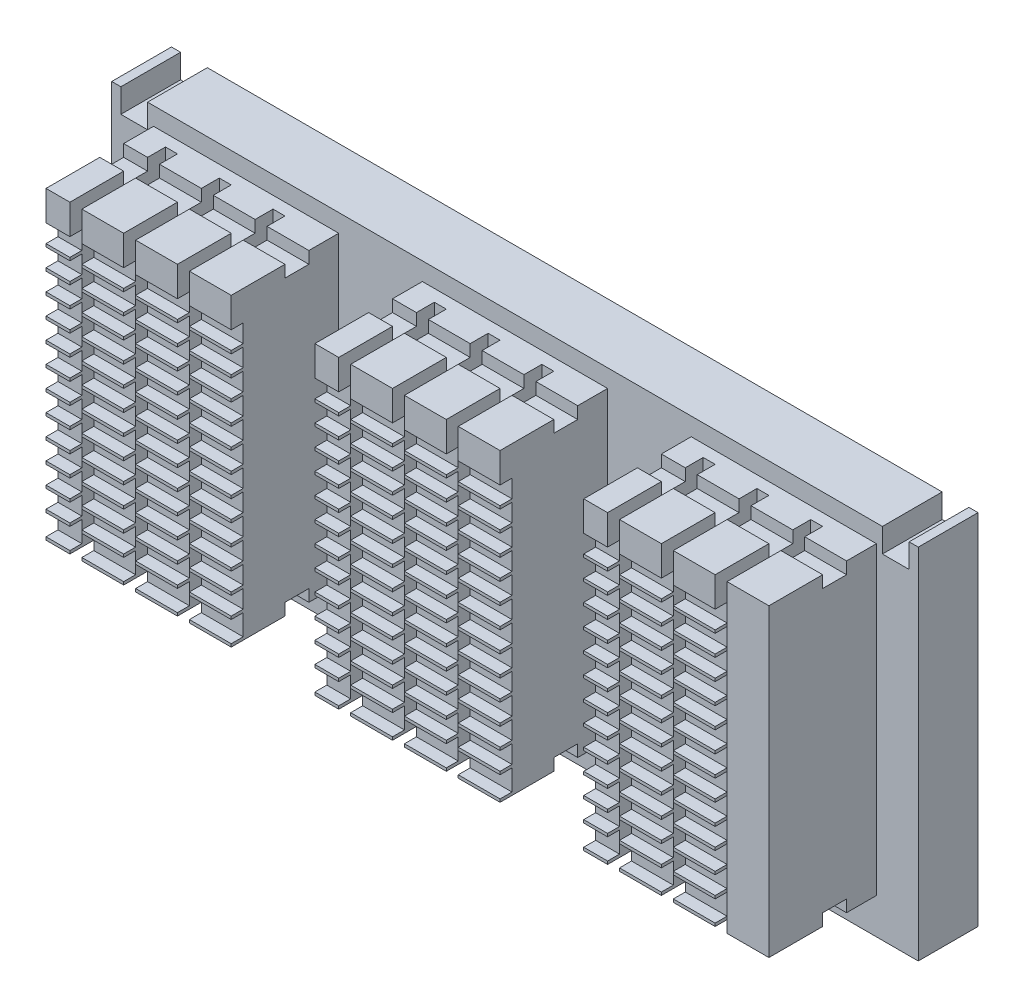
SolidWorks part; units mm, degrees
ref_plane "Front Plane" through (0, 0, 0) normal (0, 0, 1) x (1, 0, 0)
ref_plane "Top Plane" through (0, 0, 0) normal (0, 1, 0) x (1, 0, 0)
ref_plane "Right Plane" through (0, 0, 0) normal (1, 0, 0) x (0, 0, -1)
sketch "Sketch1" plane through (0, 0, 0) normal (0, 1, 0) x (1, 0, 0)
  line L1 (0, 0) -> (135, 0)
  line L2 (0, 0) -> (0, 10)
  line L3 (0, 10) -> (135, 10)
  line L4 (135, 0) -> (135, 10)
  dimension "D1" = 135
  dimension "D2" = 10
extrude "Boss-Extrude1" add sketch "Sketch1" along normal blind 60
sketch "Sketch2" plane through (0, 0, 0) normal (0, -1, 0) x (-1, 0, 0)
  line L0 (0, 10) -> (0, 0) construction
  line L1 (-134, 1) -> (-1, 1)
  line L2 (-134, 1) -> (-134, 9)
  line L3 (-134, 9) -> (-1, 9)
  line L4 (-1, 1) -> (-1, 9)
  line L5 (-135, 0) -> (-135, 10) construction
  line L6 (-135, 10) -> (0, 10) construction
  dimension "D1" = 8
  dimension "D2" = 1
  dimension "D3" = 1
  dimension "D4" = 1
extrude "Cut-Extrude1" cut sketch "Sketch2" against normal blind 50
sketch "Sketch3" plane through (0, 60, 0) normal (0, 1, 0) x (1, 0, 0)
  line L0 (135, 0) -> (135, 10) construction
  line L1 (6, 10) -> (0, 10)
  line L2 (6, 10) -> (6, 0)
  line L3 (6, 0) -> (0, 0)
  line L4 (0, 10) -> (0, 0)
  line L5 (135, 10) -> (129, 10)
  line L6 (135, 10) -> (135, 0)
  line L7 (135, 0) -> (129, 0)
  line L8 (129, 10) -> (129, 0)
  dimension "D1" = 6
  dimension "D2" = 6
extrude "Cut-Extrude2" cut sketch "Sketch3" against normal blind 4
sketch "Sketch4" plane through (0, 56, 0) normal (0, 1, 0) x (1, 0, 0)
  line L0 (6, 0) -> (6, 10) construction
  line L1 (135, 10) -> (133.47, 10)
  line L2 (135, 10) -> (135, 0)
  line L3 (135, 0) -> (133.47, 0)
  line L4 (133.47, 10) -> (133.47, 0)
  line L5 (1.5288, 10) -> (0, 10)
  line L6 (1.5288, 10) -> (1.5288, 0)
  line L7 (1.5288, 0) -> (0, 0)
  line L8 (0, 10) -> (0, 0)
  line L9 (135, 0) -> (135, 10) construction
  line L10 (129, 10) -> (129, 0) construction
  dimension "D1" = 4.4712
  dimension "D2" = 4.47
extrude "Boss-Extrude2" add sketch "Sketch4" along normal blind 4
sketch "Sketch5" plane through (0, 0, 0) normal (0, 0, 1) x (1, 0, 0)
  line L0 (0, 0) -> (135, 0) construction
  line L1 (128, 57) -> (97, 57)
  line L2 (128, 57) -> (128, 6)
  line L3 (128, 6) -> (97, 6)
  line L4 (97, 57) -> (97, 6)
  line L5 (83, 57) -> (52, 57)
  line L6 (83, 57) -> (83, 6)
  line L7 (83, 6) -> (52, 6)
  line L8 (52, 57) -> (52, 6)
  line L9 (7, 57) -> (38, 57)
  line L10 (7, 57) -> (7, 6)
  line L11 (7, 6) -> (38, 6)
  line L12 (38, 57) -> (38, 6)
  line L13 (135, 60) -> (135, 0) construction
  line L14 (0, 60) -> (0, 0) construction
  dimension "D1" = 31
  dimension "D2" = 51
  dimension "D3" = 51
  dimension "D4" = 31
  dimension "D5" = 31
  dimension "D6" = 51
  dimension "D7" = 6
  dimension "D8" = 6
  dimension "D9" = 6
  dimension "D11" = 7
  dimension "D12" = 14
  dimension "D13" = 14
extrude "Boss-Extrude4" add sketch "Sketch5" along normal blind 18
sketch "Sketch7" plane through (0, 57, 0) normal (0, 1, 0) x (1, 0, 0)
  line L0 (6, 0) -> (129, 0) construction
  line L1 (121, -2) -> (119, -2)
  line L2 (121, -2) -> (121, -18)
  line L3 (121, -18) -> (119, -18)
  line L4 (119, -2) -> (119, -18)
  line L5 (112, -2) -> (110, -2)
  line L6 (112, -2) -> (112, -18)
  line L7 (112, -18) -> (110, -18)
  line L8 (110, -2) -> (110, -18)
  line L9 (103, -2) -> (101, -2)
  line L10 (103, -2) -> (103, -18)
  line L11 (103, -18) -> (101, -18)
  line L12 (101, -2) -> (101, -18)
  line L13 (76, -2) -> (74, -2)
  line L14 (76, -2) -> (76, -18)
  line L15 (76, -18) -> (74, -18)
  line L16 (74, -2) -> (74, -18)
  line L17 (67, -2) -> (65, -2)
  line L18 (67, -2) -> (67, -18)
  line L19 (67, -18) -> (65, -18)
  line L20 (65, -2) -> (65, -18)
  line L21 (58, -2) -> (56, -2)
  line L22 (58, -2) -> (58, -18)
  line L23 (58, -18) -> (56, -18)
  line L24 (56, -2) -> (56, -18)
  line L25 (22, -2) -> (20, -2)
  line L26 (22, -2) -> (22, -18)
  line L27 (22, -18) -> (20, -18)
  line L28 (20, -2) -> (20, -18)
  line L29 (13, -2) -> (11, -2)
  line L30 (13, -2) -> (13, -18)
  line L31 (13, -18) -> (11, -18)
  line L32 (11, -2) -> (11, -18)
  line L33 (31, -2) -> (29, -2)
  line L34 (31, -2) -> (31, -18)
  line L35 (31, -18) -> (29, -18)
  line L36 (29, -2) -> (29, -18)
  line L37 (128, 0) -> (97, 0) construction
  line L38 (83, 0) -> (52, 0) construction
  line L40 (38, 0) -> (7, 0) construction
  line L41 (128, -18) -> (128, 0) construction
  line L42 (83, -18) -> (83, 0) construction
  line L43 (38, -18) -> (38, 0) construction
  line L44 (38, -18) -> (7, -18) construction
  line L45 (83, -18) -> (52, -18) construction
  line L46 (128, -18) -> (97, -18) construction
  dimension "D1" = 2
  dimension "D2" = 2
  dimension "D3" = 2
  dimension "D4" = 2
  dimension "D5" = 2
  dimension "D6" = 2
  dimension "D7" = 2
  dimension "D8" = 2
  dimension "D9" = 2
  dimension "D10" = 2
  dimension "D11" = 2
  dimension "D12" = 2
  dimension "D13" = 2
  dimension "D14" = 2
  dimension "D15" = 2
  dimension "D16" = 2
  dimension "D17" = 2
  dimension "D18" = 2
  dimension "D19" = 7
  dimension "D21" = 7
  dimension "D22" = 7
  dimension "D23" = 7
  dimension "D24" = 7
  dimension "D25" = 2
  dimension "D26" = 7
  dimension "D27" = 7
  dimension "D28" = 7
extrude "Cut-Extrude3" cut sketch "Sketch7" against normal through all
sketch "Sketch8" plane through (0, 57, 0) normal (0, 1, 0) x (1, 0, 0)
  line L0 (119, -18) -> (112, -18) construction
  line L1 (128, -5) -> (97, -5)
  line L2 (128, -5) -> (128, -9)
  line L3 (128, -9) -> (97, -9)
  line L4 (97, -5) -> (97, -9)
  line L5 (83, -5) -> (52, -5)
  line L6 (83, -5) -> (83, -9)
  line L7 (83, -9) -> (52, -9)
  line L8 (52, -5) -> (52, -9)
  line L9 (38, -5) -> (7, -5)
  line L10 (38, -5) -> (38, -9)
  line L11 (38, -9) -> (7, -9)
  line L12 (7, -5) -> (7, -9)
  line L13 (74, -18) -> (67, -18) construction
  line L14 (29, -18) -> (22, -18) construction
  line L15 (83, 0) -> (52, 0) construction
  dimension "D1" = 4
  dimension "D2" = 4
  dimension "D3" = 4
  dimension "D4" = 9
  dimension "D5" = 9
  dimension "D6" = 9
  dimension "D7" = 5
extrude "Cut-Extrude4" cut sketch "Sketch8" against normal blind 2
sketch "Sketch9" plane through (0, 6, 0) normal (0, -1, 0) x (1, 0, 0)
  line L0 (22, 18) -> (29, 18) construction
  line L1 (128, 9) -> (97, 9)
  line L2 (128, 9) -> (128, 5)
  line L3 (128, 5) -> (97, 5)
  line L4 (97, 9) -> (97, 5)
  line L5 (83, 9) -> (52, 9)
  line L6 (83, 9) -> (83, 5)
  line L7 (83, 5) -> (52, 5)
  line L8 (52, 9) -> (52, 5)
  line L9 (38, 9) -> (7, 9)
  line L10 (38, 9) -> (38, 5)
  line L11 (38, 5) -> (7, 5)
  line L12 (7, 9) -> (7, 5)
  line L13 (58, 18) -> (65, 18) construction
  line L14 (128, 18) -> (128, 0) construction
  line L16 (38, 18) -> (38, 0) construction
  line L17 (52, 18) -> (52, 0) construction
  line L18 (7, 18) -> (7, 0) construction
  line L19 (83, 18) -> (83, 0) construction
  line L20 (97, 18) -> (97, 0) construction
  line L21 (103, 18) -> (110, 18) construction
  dimension "D1" = 4
  dimension "D2" = 4
  dimension "D3" = 9
  dimension "D4" = 9
  dimension "D5" = 9
  dimension "D7" = 4
extrude "Cut-Extrude5" cut sketch "Sketch9" against normal blind 2
sketch "Sketch10" plane through (0, 0, 18) normal (0, 0, 1) x (1, 0, 0)
  line L0 (128, 52.5) -> (128, 48.5)
  line L1 (128, 56) -> (7, 56)
  line L2 (128, 56) -> (128, 52)
  line L3 (128, 52) -> (7, 52)
  line L4 (7, 56) -> (7, 52)
  line L5 (7, 57) -> (7, 6) construction
  line L6 (128, 6) -> (128, 57) construction
  line L7 (20, 57) -> (13, 57) construction
  line L8 (128, 52.5) -> (7, 52.5)
  line L9 (7, 52.5) -> (7, 48.5)
  line L10 (128, 48.5) -> (7, 48.5)
  line L11 (128, 49) -> (128, 45)
  line L12 (128, 49) -> (7, 49)
  line L13 (7, 49) -> (7, 45)
  line L14 (128, 45) -> (7, 45)
  line L15 (128, 45.5) -> (128, 41.5)
  line L16 (128, 45.5) -> (7, 45.5)
  line L17 (7, 45.5) -> (7, 41.5)
  line L18 (128, 41.5) -> (7, 41.5)
  line L19 (128, 42) -> (128, 38)
  line L20 (128, 42) -> (7, 42)
  line L21 (7, 42) -> (7, 38)
  line L22 (128, 38) -> (7, 38)
  line L23 (128, 38.5) -> (128, 34.5)
  line L24 (128, 38.5) -> (7, 38.5)
  line L25 (7, 38.5) -> (7, 34.5)
  line L26 (128, 34.5) -> (7, 34.5)
  line L27 (128, 35) -> (128, 31)
  line L28 (128, 35) -> (7, 35)
  line L29 (7, 35) -> (7, 31)
  line L30 (128, 31) -> (7, 31)
  line L31 (128, 31.5) -> (128, 27.5)
  line L32 (128, 31.5) -> (7, 31.5)
  line L33 (7, 31.5) -> (7, 27.5)
  line L34 (128, 27.5) -> (7, 27.5)
  line L35 (128, 28) -> (128, 24)
  line L36 (128, 28) -> (7, 28)
  line L37 (7, 28) -> (7, 24)
  line L38 (128, 24) -> (7, 24)
  line L39 (128, 24.5) -> (128, 20.5)
  line L40 (128, 24.5) -> (7, 24.5)
  line L41 (7, 24.5) -> (7, 20.5)
  line L42 (128, 20.5) -> (7, 20.5)
  line L43 (128, 21) -> (128, 17)
  line L44 (128, 21) -> (7, 21)
  line L45 (7, 21) -> (7, 17)
  line L46 (128, 17) -> (7, 17)
  line L47 (128, 17.5) -> (128, 13.5)
  line L48 (128, 17.5) -> (7, 17.5)
  line L49 (7, 17.5) -> (7, 13.5)
  line L50 (128, 13.5) -> (7, 13.5)
  line L51 (128, 14) -> (128, 10)
  line L52 (128, 14) -> (7, 14)
  line L53 (7, 14) -> (7, 10)
  line L54 (128, 10) -> (7, 10)
  line L55 (128, 10.5) -> (128, 6.5)
  line L56 (128, 10.5) -> (7, 10.5)
  line L57 (7, 10.5) -> (7, 6.5)
  line L58 (128, 6.5) -> (7, 6.5)
  line L59 (52, 6) -> (56, 6) construction
  dimension "D1" = 4
  dimension "D2" = 1
  dimension "D3" = 14
  dimension "D4" = 0.5
extrude "Cut-Extrude6" cut sketch "Sketch10" against normal blind 2 contours L12 L0 L3 L9 | L16 L0 L10 L13 | L20 L0 L14 L17 | L24 L0 L18 L21 | L28 L0 L22 L25 | L32 L0 L26 L29 | L36 L0 L30 L33 | L40 L0 L34 L37 | L44 L0 L38 L41 | L48 L0 L42 L45 | L56 L0 L50 L53 | L52 L0 L46 L49 | L58 L0 L54 L57
